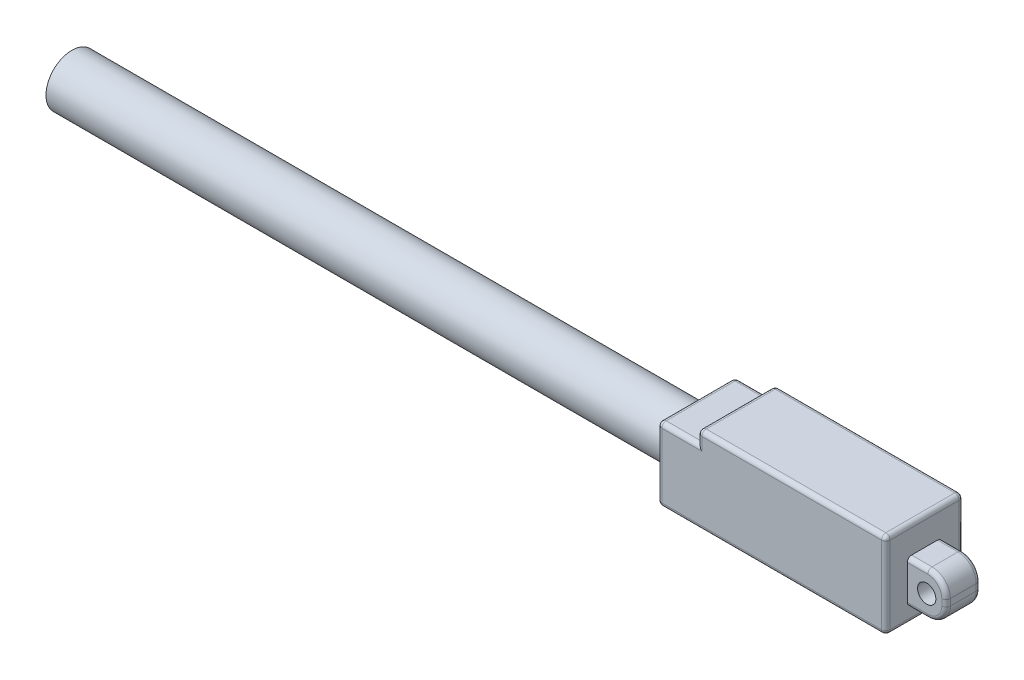
SolidWorks part; units mm, degrees
ref_plane "Front Plane" through (0, 0, 0) normal (0, 0, 1) x (1, 0, 0)
ref_plane "Top Plane" through (0, 0, 0) normal (0, 1, 0) x (1, 0, 0)
ref_plane "Right Plane" through (0, 0, 0) normal (1, 0, 0) x (0, 0, -1)
sketch "Sketch1" plane through (0, 0, 0) normal (0, 0, 1) x (1, 0, 0)
  line L1 (0, 0) -> (53, 0)
  line L2 (0, 0) -> (0, 17)
  line L3 (9.3088, 20) -> (53, 20)
  line L4 (53, 0) -> (53, 20)
  line L7 (0, 17) -> (9.3088, 17)
  line L8 (9.3088, 20) -> (9.3088, 17)
  dimension "D1" = 20
  dimension "D2" = 53
  dimension "D3" = 17
extrude "Base" add sketch "Sketch1" along normal blind 18
ref_plane "MidPlane" [suppressed] through (0, 0, 9) normal (0, 0, 1) x (1, 0, 0)
sketch "Sketch2" plane through (0, 0, 9) normal (0, 0, 1) x (1, 0, 0)
  line L0 (53, 0) -> (53, 20) construction
  line L1 (53, 0) -> (53, 17) construction
  line L2 (53, 8.5) -> (62, 8.5) construction
  line L3 (53, 13.5) -> (57.75, 13.5)
  line L4 (53, 13.5) -> (53, 3.5)
  line L5 (53, 3.5) -> (57.75, 3.5)
  line L6 (62, 9.25) -> (62, 7.75)
  line L7 (0, 17) -> (0, 0) construction
  line L8 (0, 17) -> (0, 0) construction
  line L9 (0, 17) -> (53, 17) construction
  arc A0 (57.75, 3.5) -> (62, 7.75) centre (57.75, 7.75) ccw
  arc A1 (57.75, 13.5) -> (62, 9.25) centre (57.75, 9.25) cw
  circle A2 centre (57.5, 8.5) radius 2.125
  point P10 (62, 3.5)
  point P13 (62, 13.5)
  dimension "D3" = 4.25
  dimension "D4" = 4.25
  dimension "D1" = 9
  dimension "D2" = 10
extrude "Mount" add sketch "Sketch2" along normal blind 4 and the other way blind 4
sketch "Sketch3" plane through (0, 0, 0) normal (-1, 0, 0) x (0, 0, 1)
  line L0 (0, 17) -> (18, 0) construction
  circle A0 centre (9, 8.5) radius 6
extrude "Tube" add sketch "Sketch3" along normal blind 145
ref_axis "Axis1" through (57.5, 8.5, 5) along (0, 0, 1)
fillet "Fillet1" radius 1 27 edges at (55.375, 3.5, 5) (60.7552, 4.7448, 5) (62, 8.5, 5) (55.375, 13.5, 5) (55.375, 3.5, 13) (60.7552, 4.7448, 13) (62, 8.5, 13) (55.375, 13.5, 13) (60.7552, 12.2552, 5) (60.7552, 12.2552, 13) (0, 17, 9) (0, 0, 9) (53, 20, 9) (9.3088, 20, 9) (26.5, 0, 0) (53, 10, 0) (31.1544, 20, 0) (9.3088, 18.5, 0) (4.6544, 17, 0) (0, 8.5, 0) (4.6544, 17, 18) (9.3088, 18.5, 18) (31.1544, 20, 18) (53, 10, 18) (26.5, 0, 18) (0, 8.5, 18) (53, 0, 9)
